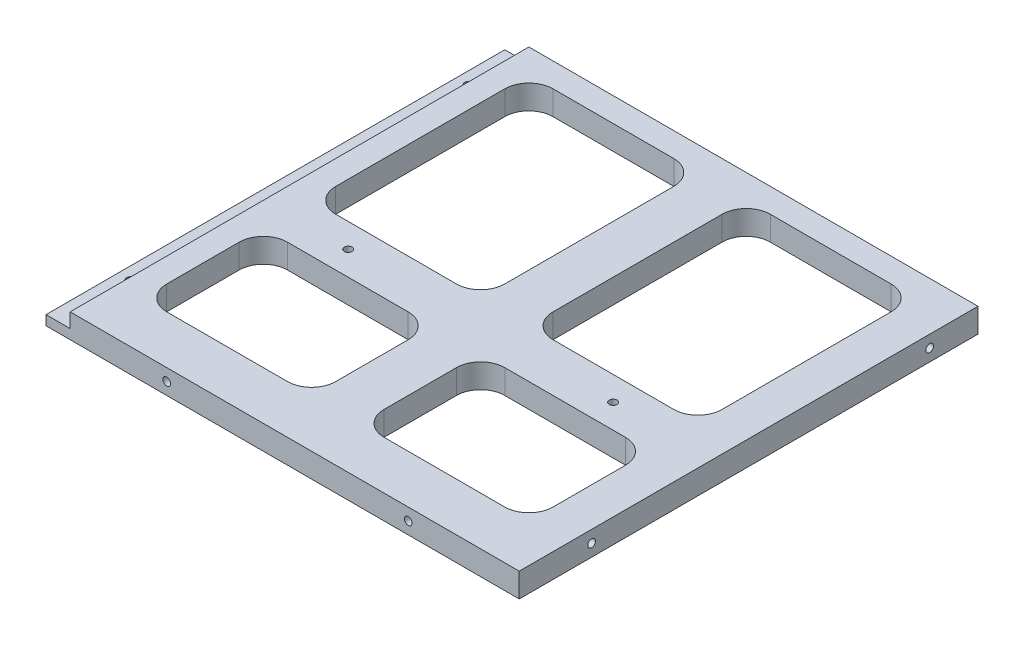
SolidWorks part; units mm, degrees
ref_plane "Front Plane" through (0, 0, 0) normal (0, 0, 1) x (1, 0, 0)
ref_plane "Top Plane" through (0, 0, 0) normal (0, 1, 0) x (1, 0, 0)
ref_plane "Right Plane" through (0, 0, 0) normal (1, 0, 0) x (0, 0, -1)
sketch "Sketch1" plane through (0, 0, 0) normal (0, 1, 0) x (1, 0, 0)
  line L1 (0, 0) -> (98, 0)
  line L2 (0, 0) -> (0, 95)
  line L3 (0, 95) -> (98, 95)
  line L4 (98, 0) -> (98, 95)
  dimension "D1" = 95
  dimension "D2" = 98
extrude "Boss-Extrude1" add sketch "Sketch1" along normal blind 5
sketch "Sketch5" plane through (0, 5, 0) normal (0, 1, 0) x (1, 0, 0)
  line L0 (98, 95) -> (0, 95) construction
  line L1 (15, 90) -> (40, 90)
  line L2 (10, 85) -> (10, 50)
  line L3 (15, 45) -> (40, 45)
  line L4 (45, 85) -> (45, 50)
  line L5 (0, 95) -> (0, 0) construction
  line L18 (60, 90) -> (85, 90)
  line L19 (0, 0) -> (98, 0) construction
  line L20 (50, 50) -> (129.5749, 50) construction
  line L21 (55, 85) -> (55, 50)
  line L22 (60, 45) -> (85, 45)
  line L23 (90, 85) -> (90, 50)
  line L24 (60, 35) -> (85, 35)
  line L25 (15, 35) -> (40, 35)
  line L26 (10, 30) -> (10, 15)
  line L27 (15, 10) -> (40, 10)
  line L28 (45, 30) -> (45, 15)
  line L29 (55, 30) -> (55, 15)
  line L30 (60, 10) -> (85, 10)
  line L31 (90, 30) -> (90, 15)
  arc A0 (15, 90) -> (10, 85) centre (15, 85) ccw
  arc A1 (10, 50) -> (15, 45) centre (15, 50) ccw
  arc A2 (40, 45) -> (45, 50) centre (40, 50) ccw
  arc A3 (40, 90) -> (45, 85) centre (40, 85) cw
  arc A4 (60, 90) -> (55, 85) centre (60, 85) ccw
  arc A5 (55, 50) -> (60, 45) centre (60, 50) ccw
  arc A6 (85, 45) -> (90, 50) centre (85, 50) ccw
  arc A7 (85, 90) -> (90, 85) centre (85, 85) cw
  arc A8 (10, 15) -> (15, 10) centre (15, 15) ccw
  arc A9 (40, 10) -> (45, 15) centre (40, 15) ccw
  arc A10 (40, 35) -> (45, 30) centre (40, 30) cw
  arc A11 (15, 35) -> (10, 30) centre (15, 30) ccw
  arc A12 (55, 15) -> (60, 10) centre (60, 15) ccw
  arc A13 (85, 10) -> (90, 15) centre (85, 15) ccw
  arc A14 (85, 35) -> (90, 30) centre (85, 30) cw
  arc A15 (60, 35) -> (55, 30) centre (60, 30) ccw
  point P55 (50, 50)
  dimension "D1" = 5
  dimension "D14" = 5
  dimension "D2" = 45
  dimension "D3" = 35
  dimension "D4" = 5
  dimension "D5" = 10
  dimension "D7" = 10
  dimension "D8" = 50
  dimension "D9" = 50
  dimension "D10" = 10
  dimension "D11" = 35
  dimension "D12" = 10
  dimension "D13" = 10
  dimension "D16" = 10
  dimension "D6" = 2
  dimension "D15" = 2
sketch "Sketch6" plane through (0, 5, 0) normal (0, 1, 0) x (1, 0, 0)
  line L0 (0, 0) -> (98, 0) construction
  line L1 (0, 95) -> (5, 95)
  line L2 (0, 95) -> (0, 0)
  line L3 (0, 0) -> (5, 0)
  line L4 (5, 95) -> (5, 0)
  dimension "D1" = 5
extrude "Cut-Extrude1" cut sketch "Sketch6" against normal blind 3
extrude "Cut-Extrude2" cut sketch "Sketch5" against normal through all
sketch "Sketch8" plane through (0, 5, 0) normal (0, 1, 0) x (1, 0, 0)
  line L2 (15, 45) -> (40, 45) construction
  line L3 (50, 50) -> (38.1732, 50) construction
  line L4 (50, 50) -> (50, 63.7417) construction
  line L5 (0, 95) -> (0, 0) construction
  line L6 (5, 0) -> (98, 0) construction
  point P2 (77.432, 40)
  point P4 (0, 0)
  point P6 (0, 0)
  point P17 (50, 50)
  point P20 (22.568, 40)
  dimension "D1" = 5
  dimension "D2" = 50
  dimension "D4" = 50
  dimension "D3" = 27.432
hole_wizard "Tap Drill for M2x0.4 Tap4" positions "3DSketch4" profile "Sketch16" hole size "M2x0.4" standard "ANSI Metric" end condition through all
sketch3d "3DSketch4"
  point P15 (22.568, 5, -40)
  point P18 (77.432, 5, -40)
sketch "Sketch16" plane through (22.568, 5, -40) normal (1, 0, 0) x (0, 0, 1)
  line L0 (0, 0) -> (0, 5)
  line L1 (0, 5) -> (0.8, 5)
  line L2 (0.8, 5) -> (0.8, 0)
  line L5 (0.8, 0) -> (0, 0)
  line L11 (0, -6.35) -> (0, 107.95) construction
  dimension "Thru Hole Dia." = 1.6
  dimension "Thru Hole Depth" = 5
sketch "Sketch11" plane through (0, 0, 0) normal (0, -1, 0) x (1, 0, 0)
  line L0 (0, -95) -> (0, 0) construction
  line L8 (0, 0) -> (98, 0) construction
  point P0 (2.5, -15)
  point P6 (2.5, -85)
  dimension "D1" = 2.5
  dimension "D2" = 70
  dimension "D3" = 15
  dimension "D4" = 2.5
hole_wizard "Tap Drill for M2x0.4 Tap1" positions "3DSketch2" profile "Sketch12" hole size "M2x0.4" standard "ANSI Metric" end condition through all
sketch3d "3DSketch2"
  point P0 (2.5, 0, -15)
  point P7 (2.5, 0, -85)
sketch "Sketch12" plane through (2.5, 0, -15) normal (1, 0, 0) x (0, 0, -1)
  line L0 (0, 0) -> (0, 5)
  line L1 (0, 5) -> (0.8, 5)
  line L2 (0.8, 5) -> (0.8, 1.1)
  line L3 (0.8, 1.1) -> (1.9, 0)
  line L5 (1.9, 0) -> (0, 0)
  line L6 (-0.8, 1.1) -> (-1.9, 0) construction
  line L11 (0, -6.35) -> (0, 107.95) construction
  dimension "Thru Hole Dia." = 1.6
  dimension "Thru Hole Depth" = 5
  dimension "Near C'Sink Dia." = 3.8
  dimension "Near C'Sink Angle" = 90
sketch "Sketch14" plane through (98, 0, 0) normal (1, 0, 0) x (0, 0, -1)
  line L0 (50, 5) -> (50, 0) construction
  line L1 (0, 5) -> (95, 5) construction
  line L4 (0, 5) -> (0, 0) construction
  point P6 (15, 2.5)
  point P7 (85, 2.5)
  dimension "D1" = 2.5
  dimension "D2" = 35
  dimension "D3" = 50
hole_wizard "Tap Drill for M2x0.4 Tap3" positions "3DSketch3" profile "Sketch15" hole size "M2x0.4" standard "ANSI Metric"
sketch3d "3DSketch3"
  point P0 (98, 2.5, -15)
  point P3 (98, 2.5, -85)
sketch "Sketch15" plane through (98, 2.5, -15) normal (0, 1, 0) x (0, 0, -1)
  line L0 (0, 0) -> (0, 6.4807)
  line L1 (0, 6.4807) -> (0.8, 6)
  line L2 (0.8, 6) -> (0.8, 0)
  line L5 (0.8, 0) -> (0, 0)
  line L10 (0, 6.4807) -> (-0.8, 6) construction
  line L11 (0, -6.35) -> (0, 107.95) construction
  dimension "Hole Dia." = 1.6
  dimension "Hole Depth" = 6
  dimension "Drill Angle" = 118
sketch "Sketch17" plane through (0, 0, -95) normal (0, 0, -1) x (-1, 0, 0)
  line L0 (-98, 0) -> (0, 0) construction
  line L1 (0, 2) -> (0, 0) construction
  line L2 (-50, 9.0434) -> (-50, -3.8001) construction
  point P0 (-7.25, 2.5)
  point P7 (-92.75, 2.5)
  dimension "D1" = 2.5
  dimension "D2" = 7.25
  dimension "D3" = 50
hole_wizard "Tap Drill for M2x0.4 Tap5" positions "3DSketch5" profile "Sketch18" hole size "M2x0.4" standard "ANSI Metric"
sketch3d "3DSketch5"
  point P0 (92.75, 2.5, -95)
  point P3 (7.25, 2.5, -95)
sketch "Sketch18" plane through (92.75, 2.5, -95) normal (1, 0, 0) x (0, 1, 0)
  line L0 (0, 0) -> (0, 4.4807)
  line L1 (0, 4.4807) -> (0.8, 4)
  line L2 (0.8, 4) -> (0.8, 0)
  line L5 (0.8, 0) -> (0, 0)
  line L10 (0, 4.4807) -> (-0.8, 4) construction
  line L11 (0, -6.35) -> (0, 107.95) construction
  dimension "Hole Dia." = 1.6
  dimension "Hole Depth" = 4
  dimension "Drill Angle" = 118
sketch "Sketch19" plane through (0, 0, 0) normal (0, 0, 1) x (1, 0, 0)
  line L0 (0, 0) -> (98, 0) construction
  line L1 (0, 2) -> (0, 0) construction
  line L2 (50, -5.0975) -> (50, 9.6857) construction
  point P0 (25, 2.5)
  point P7 (75, 2.5)
  dimension "D1" = 2.5
  dimension "D2" = 25
  dimension "D3" = 50
hole_wizard "Tap Drill for M2x0.4 Tap6" positions "3DSketch6" profile "Sketch20" hole size "M2x0.4" standard "ANSI Metric"
sketch3d "3DSketch6"
  point P0 (25, 2.5, 0)
  point P3 (75, 2.5, 0)
sketch "Sketch20" plane through (25, 2.5, 0) normal (1, 0, 0) x (0, -1, 0)
  line L0 (0, 0) -> (0, 7.4807)
  line L1 (0, 7.4807) -> (0.8, 7)
  line L2 (0.8, 7) -> (0.8, 0)
  line L5 (0.8, 0) -> (0, 0)
  line L10 (0, 7.4807) -> (-0.8, 7) construction
  line L11 (0, -6.35) -> (0, 107.95) construction
  dimension "Hole Dia." = 1.6
  dimension "Hole Depth" = 7
  dimension "Drill Angle" = 118
